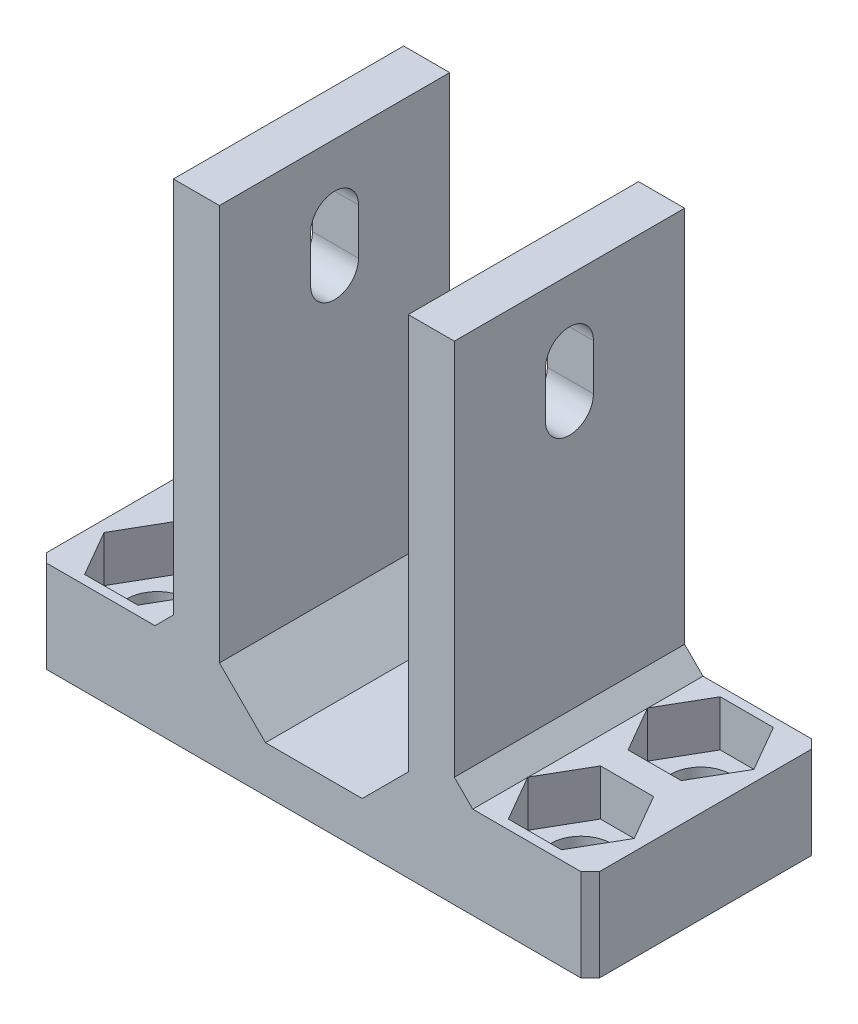
SolidWorks part; units mm, degrees
ref_plane "Front Plane" through (0, 0, 0) normal (0, 0, 1) x (1, 0, 0)
ref_plane "Top Plane" through (0, 0, 0) normal (0, 1, 0) x (1, 0, 0)
ref_plane "Right Plane" through (0, 0, 0) normal (1, 0, 0) x (0, 0, -1)
sketch "Sketch2" plane through (0, 0, 0) normal (0, 1, 0) x (1, 0, 0)
  line L1 (-30, 12.5) -> (30, 12.5)
  line L2 (-30, 12.5) -> (-30, -12.5)
  line L3 (-30, -12.5) -> (30, -12.5)
  line L4 (30, 12.5) -> (30, -12.5)
  line L5 (-30, 12.5) -> (30, -12.5) construction
  line L6 (-30, -12.5) -> (30, 12.5) construction
  line L7 (-23, 6.5) -> (23, 6.5) construction
  line L8 (-23, 6.5) -> (-23, -6.5) construction
  line L9 (-23, -6.5) -> (23, -6.5) construction
  line L10 (23, 6.5) -> (23, -6.5) construction
  line L11 (-23, 6.5) -> (23, -6.5) construction
  line L12 (-23, -6.5) -> (23, 6.5) construction
  circle A0 centre (-23, 6.5) radius 3.3
  circle A1 centre (23, 6.5) radius 3.3
  circle A2 centre (-23, -6.5) radius 3.3
  circle A3 centre (23, -6.5) radius 3.3
  point P0 (0, 0)
  point P12 (0, 0)
  point P13 (0, 0)
  point P14 (24.6526, 6.5)
  point P15 (0, 0)
  point P17 (0, 0)
  dimension "D5" = 6.6
  dimension "D1" = 25
  dimension "D2" = 60
  dimension "D3" = 46
  dimension "D4" = 13
extrude "Boss-Extrude2" add sketch "Sketch2" along normal blind 5
sketch "Sketch3" plane through (0, 0, 12.5) normal (0, 0, 1) x (1, 0, 0)
  line L0 (-30, 5) -> (30, 5) construction
  line L1 (-15.25, 5) -> (-10.25, 5)
  line L2 (-15.25, 5) -> (-15.25, 53)
  line L3 (-15.25, 53) -> (-10.25, 53)
  line L4 (-10.25, 5) -> (-10.25, 53)
  line L5 (0, 0) -> (0, -12.3291) construction
  line L6 (10.25, 5) -> (15.25, 5)
  line L7 (10.25, 5) -> (10.25, 53)
  line L8 (10.25, 53) -> (15.25, 53)
  line L9 (15.25, 5) -> (15.25, 53)
  dimension "D1" = 20.5
  dimension "D2" = 5
  dimension "D3" = 48
extrude "Boss-Extrude3" add sketch "Sketch3" against normal up to surface (25 mm away) up to face at (0, 2.5, -12.5)
sketch "Sketch4" plane through (15.25, 0, 0) normal (1, 0, 0) x (0, 0, -1)
  line L0 (0, 45.5) -> (0, 40.5) construction
  line L1 (2.6, 45.5) -> (2.6, 40.5)
  line L2 (-2.6, 45.5) -> (-2.6, 40.5)
  line L3 (12.5, 53) -> (-12.5, 53) construction
  arc A0 (2.6, 45.5) -> (-2.6, 45.5) centre (0, 45.5) ccw
  arc A1 (-2.6, 40.5) -> (2.6, 40.5) centre (0, 40.5) ccw
  point P3 (0, 43)
  dimension "D1" = 5.2
  dimension "D2" = 10
  dimension "D3" = 5
extrude "Cut-Extrude1" cut sketch "Sketch4" against normal up to surface (30.5 mm away) up to face at (-15.25, 29, 0)
sketch "Sketch5" plane through (0, 5, 0) normal (0, 1, 0) x (1, 0, 0)
  line L0 (30, 12.5) -> (15.25, 12.5) construction
  line L1 (15.25, 12.5) -> (15.25, -12.5) construction
  line L2 (15.25, -12.5) -> (30, -12.5) construction
  line L3 (30, -12.5) -> (30, 12.5) construction
  line L4 (-15.25, -12.5) -> (-15.25, 12.5) construction
  line L5 (-15.25, 12.5) -> (-30, 12.5) construction
  line L6 (-30, 12.5) -> (-30, -12.5) construction
  line L7 (-30, -12.5) -> (-15.25, -12.5) construction
  line L8 (30, 12.5) -> (15.25, 12.5)
  line L9 (15.25, 12.5) -> (15.25, -12.5)
  line L10 (15.25, -12.5) -> (30, -12.5)
  line L11 (30, -12.5) -> (30, 12.5)
  line L12 (-15.25, -12.5) -> (-15.25, 12.5)
  line L13 (-15.25, 12.5) -> (-30, 12.5)
  line L14 (-30, 12.5) -> (-30, -12.5)
  line L15 (-30, -12.5) -> (-15.25, -12.5)
  line L16 (-30, 0) -> (30, 0) construction
  line L23 (28.7735, 6.5) -> (25.8868, 11.5)
  line L24 (25.8868, 11.5) -> (20.1132, 11.5)
  line L25 (20.1132, 11.5) -> (17.2265, 6.5)
  line L26 (17.2265, 6.5) -> (20.1132, 1.5)
  line L27 (20.1132, 1.5) -> (25.8868, 1.5)
  line L28 (25.8868, 1.5) -> (28.7735, 6.5)
  line L29 (-17.2265, 6.5) -> (-20.1132, 11.5)
  line L30 (-20.1132, 11.5) -> (-25.8868, 11.5)
  line L31 (-25.8868, 11.5) -> (-28.7735, 6.5)
  line L32 (-28.7735, 6.5) -> (-25.8868, 1.5)
  line L33 (-25.8868, 1.5) -> (-20.1132, 1.5)
  line L34 (-20.1132, 1.5) -> (-17.2265, 6.5)
  line L35 (25.8868, -1.5) -> (28.7735, -6.5)
  line L36 (20.1132, -1.5) -> (25.8868, -1.5)
  line L37 (17.2265, -6.5) -> (20.1132, -1.5)
  line L38 (20.1132, -11.5) -> (17.2265, -6.5)
  line L39 (25.8868, -11.5) -> (20.1132, -11.5)
  line L40 (28.7735, -6.5) -> (25.8868, -11.5)
  line L41 (-20.1132, -1.5) -> (-17.2265, -6.5)
  line L42 (-25.8868, -1.5) -> (-20.1132, -1.5)
  line L43 (-28.7735, -6.5) -> (-25.8868, -1.5)
  line L44 (-25.8868, -11.5) -> (-28.7735, -6.5)
  line L45 (-20.1132, -11.5) -> (-25.8868, -11.5)
  line L46 (-17.2265, -6.5) -> (-20.1132, -11.5)
  circle A0 centre (-23, 6.5) radius 5 construction
  circle A1 centre (23, 6.5) radius 5 construction
  dimension "D1" = 10
  dimension "D2" = 10
extrude "Boss-Extrude4" add sketch "Sketch5" along normal blind 5
chamfer "Chamfer1" distance 2 angle 45 2 edges at (15.25, 10, 0) (-15.25, 10, 0)
chamfer "Chamfer2" distance 5 angle 45 2 edges at (10.25, 5, 0) (-10.25, 5, 0)
chamfer "Chamfer3" distance 1 angle 45 4 edges at (30, 5, -12.5) (-30, 5, -12.5) (30, 5, 12.5) (-30, 5, 12.5)
